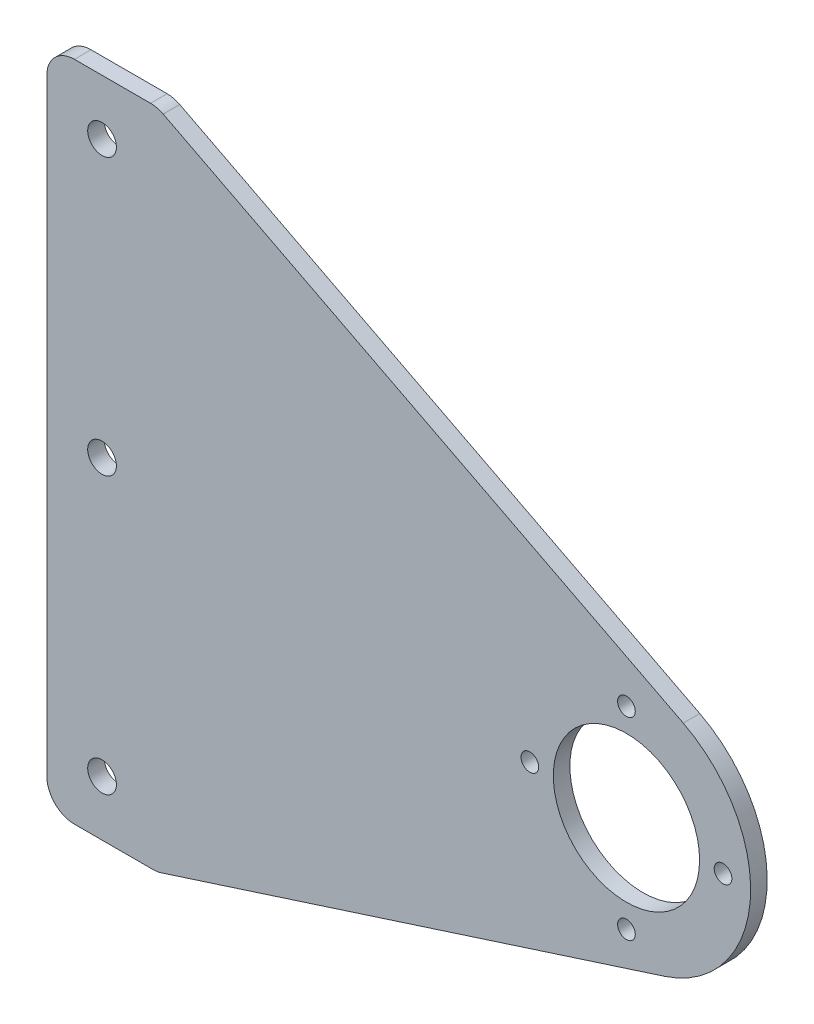
SolidWorks part; units mm, degrees
ref_plane "正面" through (0, 0, 0) normal (0, 0, 1) x (1, 0, 0)
ref_plane "平面" through (0, 0, 0) normal (0, 1, 0) x (1, 0, 0)
ref_plane "右側面" through (0, 0, 0) normal (1, 0, 0) x (0, 0, -1)
sketch "ｽｹｯﾁ2" plane through (0, 0, 0) normal (0, 0, 1) x (1, 0, 0)
  line L0 (17.5, 0) -> (-17.5, 0) construction
  line L1 (0, -17.5) -> (0, 17.5) construction
  line L2 (0, 0) -> (-85, 9) construction
  line L3 (-95, -41) -> (-95, 9) construction
  line L4 (-95, 9) -> (-95, 59) construction
  line L5 (-105, 69) -> (-105, -51)
  line L6 (-105, -51) -> (-85, -51)
  line L7 (-105, 69) -> (-85, 69)
  line L8 (-85, 69) -> (-85, -51) construction
  line L9 (-85, 69) -> (10.2878, 20.0103)
  line L10 (-85, -51) -> (6.8947, -21.4176)
  line L11 (-105, 9) -> (-85, 9) construction
  line L12 (0, -22.5) -> (-105, -22.5) construction
  line L13 (-105, -22.5) -> (-105, -51) construction
  line L14 (0, -76) -> (-105, -76) construction
  line L15 (-105, -76) -> (-105, -51) construction
  circle A0 centre (0, 0) radius 13.25
  circle A1 centre (0, 17.5) radius 1.6
  circle A2 centre (17.5, 0) radius 1.6
  circle A3 centre (0, -17.5) radius 1.6
  circle A4 centre (-17.5, 0) radius 1.6
  circle A5 centre (-95, 9) radius 2.6
  circle A6 centre (-95, 59) radius 2.6
  circle A7 centre (-95, -41) radius 2.6
  arc A8 (6.8947, -21.4176) -> (10.2878, 20.0103) centre (0, 0) ccw
  circle A9 centre (0, 0) radius 76 construction
  point P6 (0, 0)
  point P9 (0, 0)
  point P29 (-95, 9)
  dimension "D1" = 26.5
  dimension "D2" = 3.2
  dimension "D3" = 5.2
  dimension "D4" = 50
  dimension "D5" = 50
  dimension "D8" = 22.5
  dimension "D9" = 20
  dimension "D11" = 10
  dimension "D12" = 152
  dimension "D13" = 105
  dimension "D6" = 90
  dimension "D7" = 35
  dimension "D10" = 10
  dimension "D14" = 25
extrude "ﾎﾞｽ - 押し出し1" add sketch "ｽｹｯﾁ2" along normal blind 3
fillet "ﾌｨﾚｯﾄ3" radius 5 4 edges at (-85, 69, 1.5) (-85, -51, 1.5) (-105, -51, 1.5) (-105, 69, 1.5)
